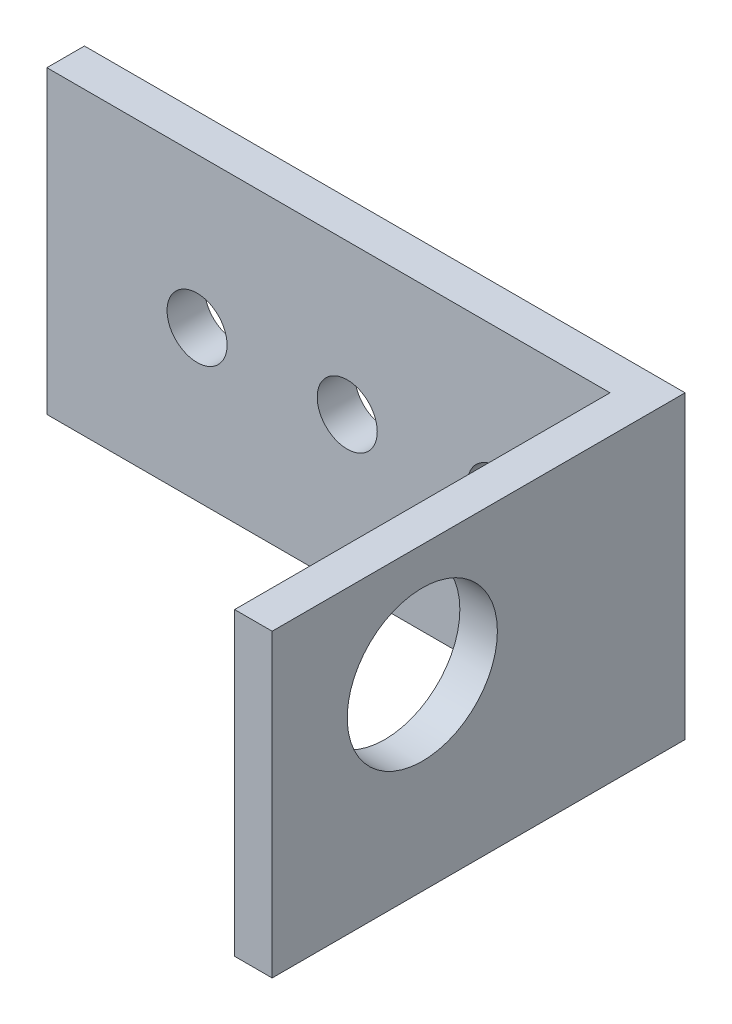
SolidWorks part; units mm, degrees
material "6061-T6 (SS)"
ref_plane "Front Plane" through (0, 0, 0) normal (0, 0, 1) x (1, 0, 0)
ref_plane "Top Plane" through (0, 0, 0) normal (0, 1, 0) x (1, 0, 0)
ref_plane "Right Plane" through (0, 0, 0) normal (1, 0, 0) x (0, 0, -1)
sketch "Sketch1" plane through (0, 0, 0) normal (0, 1, 0) x (1, 0, 0)
  line L1 (-25.4, -17.4625) -> (25.4, -17.4625)
  line L2 (-25.4, -17.4625) -> (-25.4, 17.4625)
  line L3 (-25.4, 17.4625) -> (25.4, 17.4625)
  line L4 (25.4, -17.4625) -> (25.4, 17.4625)
  line L5 (-25.4, -17.4625) -> (25.4, 17.4625) construction
  line L6 (-25.4, 17.4625) -> (25.4, -17.4625) construction
  line L7 (-25.4, -17.4625) -> (22.225, -17.4625)
  line L8 (-25.4, -17.4625) -> (-25.4, 14.2875)
  line L9 (-25.4, 14.2875) -> (22.225, 14.2875)
  line L10 (22.225, -17.4625) -> (22.225, 14.2875)
  point P0 (0, 0)
  dimension "D1" = 50.8
  dimension "D2" = 34.925
  dimension "D3" = 47.625
  dimension "D4" = 31.75
extrude "Boss-Extrude1" add sketch "Sketch1" along normal blind 25.4 contours L10 L1 L4 L3 L2 L9 region at (22.8415, 0, 1.5875)
sketch "Sketch2" plane through (25.4, 0, 0) normal (1, 0, 0) x (0, 0, -1)
  line L0 (-17.4625, 25.4) -> (17.4625, 25.4) construction
  line L1 (-17.4625, 25.4) -> (-17.4625, 0) construction
  circle A0 centre (-4.7625, 15.875) radius 6.35
  dimension "D1" = 12.7
  dimension "D2" = 9.525
  dimension "D3" = 12.7
extrude "Cut-Extrude1" cut sketch "Sketch2" against normal up to surface (3.175 mm away) up to face at (22.225, 12.7, 1.5875)
sketch "Sketch3" plane through (0, 0, -14.2875) normal (0, 0, 1) x (1, 0, 0)
  line L0 (-25.4, 25.4) -> (-25.4, 0) construction
  line L1 (-25.4, 0) -> (22.225, 0) construction
  circle A0 centre (-12.7, 12.7) radius 2.54
  circle A1 centre (0, 12.7) radius 2.54
  circle A2 centre (12.7, 12.7) radius 2.54
  dimension "D1" = 5.08
  dimension "D2" = 12.7
  dimension "D3" = 12.7
  dimension "D4" = 12.7
  dimension "D5" = 12.7
extrude "Cut-Extrude2" cut sketch "Sketch3" against normal up to surface (3.175 mm away) up to face at (0, 12.7, -17.4625)
